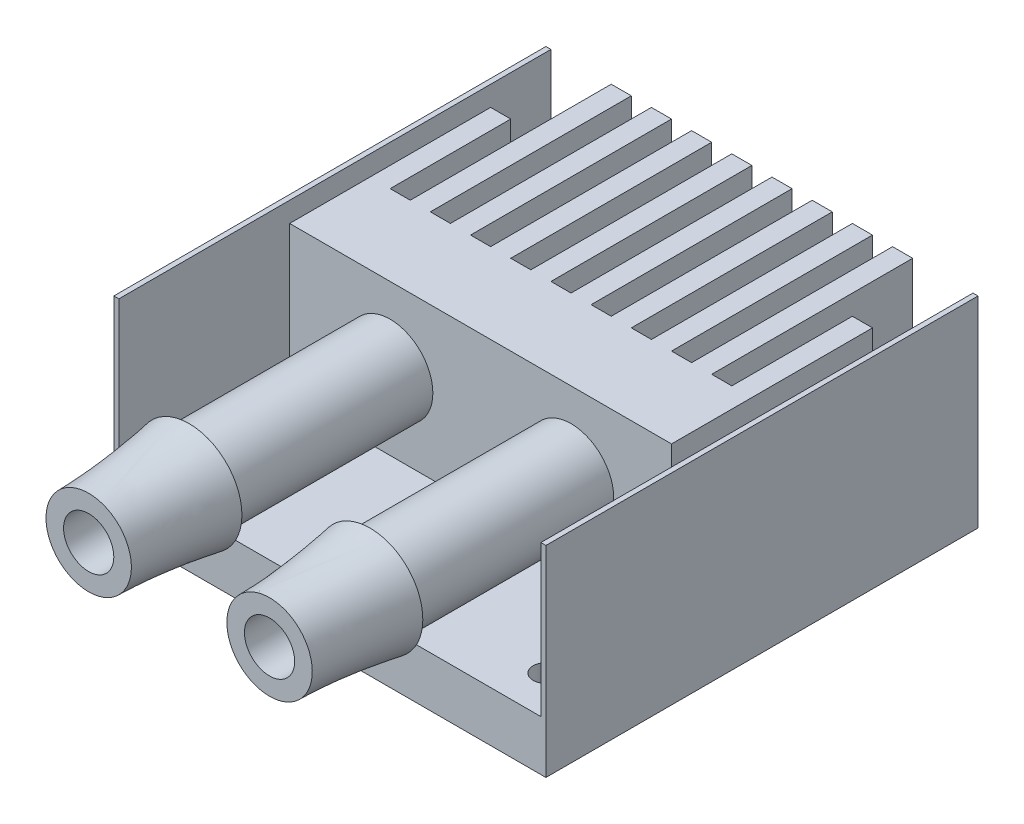
SolidWorks part; units mm, degrees
ref_plane "Front Plane" through (0, 0, 0) normal (0, 0, 1) x (1, 0, 0)
ref_plane "Top Plane" through (0, 0, 0) normal (0, 1, 0) x (1, 0, 0)
ref_plane "Right Plane" through (0, 0, 0) normal (1, 0, 0) x (0, 0, -1)
sketch "Sketch1" plane through (0, 0, 0) normal (0, 1, 0) x (1, 0, 0)
  line L1 (-21.5, 21.5) -> (21.5, 21.5)
  line L2 (-21.5, 21.5) -> (-21.5, -21.5)
  line L3 (-21.5, -21.5) -> (21.5, -21.5)
  line L4 (21.5, 21.5) -> (21.5, -21.5)
  line L5 (-21.5, 21.5) -> (21.5, -21.5) construction
  line L6 (-21.5, -21.5) -> (21.5, 21.5) construction
  point P0 (0, 0)
  dimension "D1" = 43
extrude "Boss-Extrude1" add sketch "Sketch1" along normal blind 20
sketch "Sketch2" plane through (0, 0, -21.5) normal (0, 0, -1) x (-1, 0, 0)
  line L0 (-21.5, 20) -> (21.5, 20) construction
  line L1 (-1, 20) -> (1, 20)
  line L2 (-1, 20) -> (-1, 5)
  line L3 (-1, 5) -> (1, 5)
  line L4 (1, 20) -> (1, 5)
  line L25 (-1, 10) -> (-1, 4)
  line L26 (-1, 10) -> (1, 10)
  line L28 (-1, 4) -> (1, 4)
  line L73 (-1, 10) -> (-1, 4)
  line L74 (-1, 10) -> (1, 10)
  line L75 (1, 10) -> (1, 4)
  line L76 (-1, 4) -> (1, 4)
  line L97 (-1, 10) -> (-1, 4)
  line L98 (-1, 10) -> (1, 10)
  line L99 (1, 10) -> (1, 4)
  line L100 (-1, 4) -> (1, 4)
  line L121 (-1, 10) -> (-1, 4)
  line L122 (-1, 10) -> (1, 10)
  line L123 (1, 10) -> (1, 4)
  line L124 (-1, 4) -> (1, 4)
  point P6 (0, 20)
  dimension "D1" = 2
  dimension "D2" = 15
extrude "Cut-Extrude1" cut sketch "Sketch2" against normal blind 20 contours L4 L3 L2 L1
pattern_linear "LPattern1" count 6 spacing 4 along (1, 0, 0) of "Cut-Extrude1"
mirror "Mirror1" about plane through (0, 0, 0) normal (1, 0, 0) of "LPattern1"
sketch "Sketch7" plane through (0, 0, -1.5) normal (0, 0, -1) x (-1, 0, 0)
  line L0 (21, 20) -> (19, 20) construction
  line L1 (19, 20) -> (19, 5) construction
  line L2 (19, 5) -> (21, 5) construction
  line L3 (21, 5) -> (21, 20) construction
  line L4 (-19, 20) -> (-21, 20) construction
  line L5 (-21, 20) -> (-21, 5) construction
  line L6 (-21, 5) -> (-19, 5) construction
  line L7 (-19, 5) -> (-19, 20) construction
  line L8 (21, 20) -> (19, 20)
  line L9 (19, 20) -> (19, 5)
  line L10 (19, 5) -> (21, 5)
  line L11 (21, 5) -> (21, 20)
  line L12 (-19, 20) -> (-21, 20)
  line L13 (-21, 20) -> (-21, 5)
  line L14 (-21, 5) -> (-19, 5)
  line L15 (-19, 5) -> (-19, 20)
extrude "Cut-Extrude6" cut sketch "Sketch7" against normal through all
sketch "Sketch8" plane through (0, 0, 21.5) normal (0, 0, 1) x (1, 0, 0)
  line L1 (-19, 20) -> (19, 20)
  line L2 (-19, 20) -> (-19, 5)
  line L3 (-19, 5) -> (19, 5)
  line L4 (19, 20) -> (19, 5)
extrude "Cut-Extrude7" cut sketch "Sketch8" against normal blind 15
sketch "Sketch9" plane through (0, 0, 6.5) normal (0, 0, 1) x (1, 0, 0)
  line L0 (-19, 12.5) -> (-9, 12.5) construction
  line L1 (-19, 20) -> (-19, 5) construction
  circle A0 centre (-9, 12.5) radius 4.25
  dimension "D2" = 8.5
  dimension "D1" = 10
extrude "Boss-Extrude2" add sketch "Sketch9" along normal blind 20
ref_plane "Plane1" through (0, 0, 36.5) normal (0, 0, 1) x (1, 0, 0)
sketch "Sketch10" plane through (0, 0, 36.5) normal (0, 0, 1) x (1, 0, 0)
  circle A0 centre (-9, 12.5) radius 4.25
  circle A1 centre (-9, 12.5) radius 4.25 construction
  point P5 (0, 0)
sketch "Sketch11" plane through (0, 0, 26.5) normal (0, 0, 1) x (1, 0, 0)
  circle A0 centre (-9, 12.5) radius 5.25
  circle A1 centre (-9, 12.5) radius 4.25 construction
  dimension "D1" = 1
loft "Loft1" add profiles "Sketch11", "Sketch10" connector at (-10.3503, 17.5734, 26.5) connector at (-7.6968, 16.5453, 36.5)
sketch "Sketch12" plane through (0, 0, 36.5) normal (0, 0, 1) x (1, 0, 0)
  circle A3 centre (-9, 12.5) radius 2.5
  circle A4 centre (-9, 12.5) radius 4.25 construction
  point P2 (0, 0)
  dimension "D1" = 5
extrude "Cut-Extrude8" cut sketch "Sketch12" against normal blind 35 contours A3
mirror "Mirror3" about plane through (0, 0, 0) normal (1, 0, 0) of "Boss-Extrude2", "Loft1", "Cut-Extrude8"
sketch "Sketch13" plane through (0, 0, 0) normal (0, -1, 0) x (1, 0, 0)
  line L1 (-17.5, 17.5) -> (17.5, 17.5) construction
  line L2 (-17.5, 17.5) -> (-17.5, -17.5) construction
  line L3 (-17.5, -17.5) -> (17.5, -17.5) construction
  line L4 (17.5, 17.5) -> (17.5, -17.5) construction
  line L5 (-17.5, 17.5) -> (17.5, -17.5) construction
  line L6 (-17.5, -17.5) -> (17.5, 17.5) construction
  circle A0 centre (17.5, 17.5) radius 1.27
  circle A1 centre (-17.5, 17.5) radius 1.27
  circle A2 centre (-17.5, -17.5) radius 1.27
  circle A3 centre (17.5, -17.5) radius 1.27
  point P0 (0, 0)
  dimension "D2" = 2.54
  dimension "D1" = 35
extrude "Cut-Extrude9" cut sketch "Sketch13" against normal through all
sketch "Sketch14" plane through (0, 20, 0) normal (0, 1, 0) x (1, 0, 0)
  line L0 (-17, 1.5) -> (-17, 16.3326) construction
  line L1 (-19, 21.5) -> (-17, 21.5)
  line L2 (-19, 21.5) -> (-19, 13.5)
  line L3 (-19, 13.5) -> (-17, 13.5)
  line L4 (-17, 21.5) -> (-17, 13.5)
  line L5 (19, -6.5) -> (19, 21.5) construction
  line L6 (17, 21.5) -> (19, 21.5)
  line L7 (17, 21.5) -> (17, 13.5)
  line L8 (17, 13.5) -> (19, 13.5)
  line L9 (19, 21.5) -> (19, 13.5)
  dimension "D1" = 8
extrude "Cut-Extrude10" cut sketch "Sketch14" against normal up to surface (15 mm away) up to face at (-16.205, 5, -13.5)
